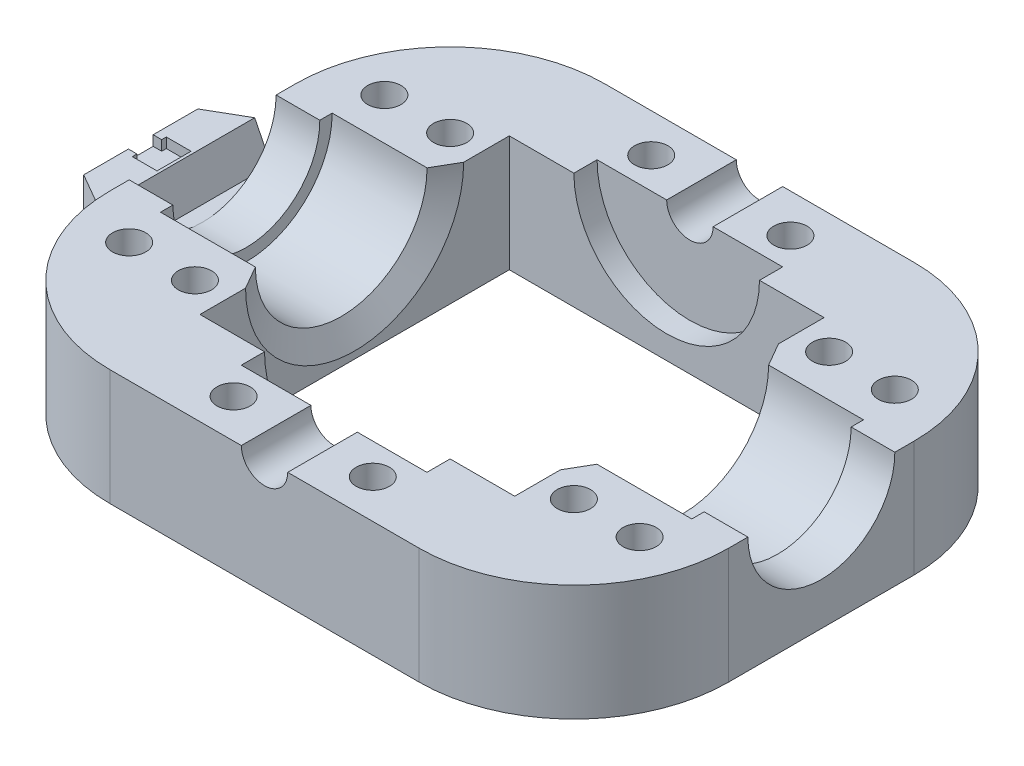
SolidWorks part; units mm, degrees
ref_plane "Спереди" through (0, 0, 0) normal (0, 0, 1) x (1, 0, 0)
ref_plane "Сверху" through (0, 0, 0) normal (0, 1, 0) x (1, 0, 0)
ref_plane "Справа" through (0, 0, 0) normal (1, 0, 0) x (0, 0, -1)
sketch "Sketch1" plane through (0, 0, 0) normal (0, 1, 0) x (1, 0, 0)
  line L1 (40, -32) -> (-40, -32)
  line L2 (40, -32) -> (40, 32)
  line L3 (40, 32) -> (-40, 32)
  line L4 (-40, -32) -> (-40, 32)
  line L5 (40, -32) -> (-40, 32) construction
  line L6 (40, 32) -> (-40, -32) construction
  line L7 (20.35, -20) -> (-20.35, -20)
  line L8 (20.35, -20) -> (20.35, 20)
  line L9 (20.35, 20) -> (-20.35, 20)
  line L10 (-20.35, -20) -> (-20.35, 20)
  line L11 (20.35, -20) -> (-20.35, 20) construction
  line L12 (20.35, 20) -> (-20.35, -20) construction
  point P0 (0, 0)
  point P6 (0, 0)
  dimension "D1" = 80
  dimension "D2" = 64
  dimension "D3" = 40
  dimension "D4" = 40.7
extrude "Boss-Extrude1" add sketch "Sketch1" along normal blind 15
sketch "Sketch3" plane through (0, 15, 0) normal (0, 1, 0) x (1, 0, 0)
  line L0 (-20.35, 0) -> (-40, 0) construction
  line L1 (-20.35, 20) -> (-20.35, -20) construction
  line L2 (-40, 32) -> (-40, -32) construction
  line L3 (20.35, 0) -> (40, 0) construction
  line L4 (20.35, -20) -> (20.35, 20) construction
  line L5 (40, -32) -> (40, 32) construction
  line L10 (20.35, -11.1) -> (34.35, -11.1)
  line L11 (20.35, -11.1) -> (20.35, 0)
  line L12 (20.35, 0) -> (34.35, 0)
  line L13 (34.35, -11.1) -> (34.35, 0)
  line L14 (20.35, -11.1) -> (34.35, 0) construction
  line L15 (20.35, 0) -> (34.35, -11.1) construction
  line L16 (-34.35, -11.1) -> (-20.35, -11.1)
  line L17 (-34.35, -11.1) -> (-34.35, 0)
  line L18 (-34.35, 0) -> (-20.35, 0)
  line L19 (-20.35, -11.1) -> (-20.35, 0)
  line L20 (-34.35, -11.1) -> (-20.35, 0) construction
  line L21 (-34.35, 0) -> (-20.35, -11.1) construction
  point P18 (27.35, -5.55)
  point P23 (-27.35, -5.55)
  dimension "D1" = 14
  dimension "D2" = 11.1
revolve "Cut-Revolve1" cut sketch "Sketch3" angle 360 about L12
sketch "Sketch4" plane through (40, 0, 0) normal (1, 0, 0) x (0, 0, -1)
  line L0 (-32, 15) -> (32, 15) construction
  circle A0 centre (0, 15) radius 9.5
  dimension "D1" = 19
extrude "Cut-Extrude2" cut sketch "Sketch4" against normal through all
sketch "Sketch5" plane through (0, 0, 32) normal (0, 0, 1) x (1, 0, 0)
  line L0 (-40, 15) -> (40, 15) construction
  circle A0 centre (0, 15) radius 3
  dimension "D1" = 6
extrude "Cut-Extrude3" cut sketch "Sketch5" against normal through all
sketch "Sketch8" plane through (0, 15, 0) normal (0, 1, 0) x (1, 0, 0)
  line L1 (-24.5, -16.5) -> (24.5, -16.5) construction
  line L2 (-24.5, -16.5) -> (-24.5, 16.5) construction
  line L3 (-24.5, 16.5) -> (24.5, 16.5) construction
  line L4 (24.5, -16.5) -> (24.5, 16.5) construction
  line L5 (-24.5, -16.5) -> (24.5, 16.5) construction
  line L6 (-24.5, 16.5) -> (24.5, -16.5) construction
  line L7 (-9, 27) -> (9, 27) construction
  line L8 (-9, 27) -> (-9, -27) construction
  line L9 (-9, -27) -> (9, -27) construction
  line L10 (9, 27) -> (9, -27) construction
  line L11 (-9, 27) -> (9, -27) construction
  line L12 (-9, -27) -> (9, 27) construction
  line L13 (33, -16.5) -> (-33, -16.5) construction
  line L14 (33, -16.5) -> (33, 16.5) construction
  line L15 (33, 16.5) -> (-33, 16.5) construction
  line L16 (-33, -16.5) -> (-33, 16.5) construction
  line L17 (33, -16.5) -> (-33, 16.5) construction
  line L18 (33, 16.5) -> (-33, -16.5) construction
  circle A0 centre (24.5, 16.5) radius 2.15
  circle A1 centre (24.5, -16.5) radius 2.15
  circle A2 centre (-24.5, -16.5) radius 2.15
  circle A3 centre (-24.5, 16.5) radius 2.15
  circle A4 centre (9, -27) radius 2.15
  circle A5 centre (-9, -27) radius 2.15
  circle A6 centre (-9, 27) radius 2.15
  circle A7 centre (9, 27) radius 2.15
  circle A8 centre (-33, 16.5) radius 2.15
  circle A9 centre (-33, -16.5) radius 2.15
  circle A10 centre (33, -16.5) radius 2.15
  circle A11 centre (33, 16.5) radius 2.15
  point P0 (0, 0)
  point P10 (0, 0)
  point P16 (0, 0)
  dimension "D3" = 4.3
  dimension "D1" = 33
  dimension "D2" = 49
  dimension "D4" = 18
  dimension "D5" = 54
  dimension "D6" = 66
extrude "Cut-Extrude6" cut sketch "Sketch8" against normal through all
fillet "Fillet1" radius 20 4 edges at (-40, 7.5, 32) (-40, 7.5, -32) (40, 7.5, -32) (40, 7.5, 32)
chamfer "Chamfer1" distance 3 angle 30 2 edges at (-20.35, 3.9, 0) (20.35, 3.9, 0) first distance on face at (-20.35, 8.15, 0) first distance on face at (20.35, 8.15, 0)
sketch "Sketch9" plane through (0, 15, 0) normal (0, 1, 0) x (1, 0, 0)
  line L0 (0, 29.8714) -> (0, -31.0419) construction
  line L1 (-3, 20) -> (-20.35, 20) construction
  line L2 (-12, -23) -> (0, -23)
  line L3 (-12, -23) -> (-12, -20)
  line L4 (-12, -20) -> (0, -20)
  line L5 (0, -23) -> (0, -20)
  line L6 (-12, -23) -> (0, -20) construction
  line L7 (-12, -20) -> (0, -23) construction
  line L8 (-12, 20) -> (0, 20)
  line L9 (-12, 20) -> (-12, 23)
  line L10 (-12, 23) -> (0, 23)
  line L11 (0, 20) -> (0, 23)
  line L12 (-12, 20) -> (0, 23) construction
  line L13 (-12, 23) -> (0, 20) construction
  line L14 (-20.35, -20) -> (-3, -20) construction
  point P3 (-6, -21.5)
  point P8 (-6, 21.5)
  dimension "D1" = 3
  dimension "D2" = 12
revolve "Cut-Revolve2" cut sketch "Sketch9" angle 360 about L0 other way angle 360
sketch "Sketch10" plane through (-40, 0, 0) normal (-1, 0, 0) x (0, 0, 1)
  line L0 (-9.5, 15) -> (9.5, 15) construction
  line L1 (0, 15) -> (0, 0) construction
  line L2 (-12, 0) -> (12, 0) construction
  line L4 (12, 5.5) -> (-12, 5.5)
  line L5 (12, 5.5) -> (12, 0)
  line L6 (12, 0) -> (-12, 0)
  line L7 (-12, 5.5) -> (-12, 0)
  line L8 (12, 5.5) -> (-12, 0) construction
  line L9 (12, 0) -> (-12, 5.5) construction
  arc A0 (-9.5, 15) -> (9.5, 15) centre (0, 15) ccw construction
  point P8 (0, 2.75)
extrude "Boss-Extrude2" add sketch "Sketch10" along normal blind 8
sketch "Sketch12" plane through (-40, 0, 0) normal (-1, 0, 0) x (0, 0, 1)
  line L0 (-9.5, 15) -> (9.5, 15) construction
  line L1 (0, 15) -> (0, 0) construction
  line L3 (12, 9.2) -> (-12, 9.2)
  line L4 (12, 9.2) -> (12, 5.5)
  line L5 (12, 5.5) -> (-12, 5.5)
  line L6 (-12, 9.2) -> (-12, 5.5)
  line L7 (12, 9.2) -> (-12, 5.5) construction
  line L8 (12, 5.5) -> (-12, 9.2) construction
  point P7 (0, 7.35)
  dimension "D1" = 5.8
extrude "Boss-Extrude3" add sketch "Sketch12" along normal up to surface (8 mm away) from offset 2 up to face at (-48, 2.75, 0)
sketch "Sketch13" plane through (0, 9.2, 0) normal (0, 1, 0) x (1, 0, 0)
  line L0 (-42, 0) -> (-48, 0) construction
  line L1 (-42, -12) -> (-42, 12) construction
  line L2 (-48, 12) -> (-48, -12) construction
  line L3 (-46.9, 2.2) -> (-46.9, 1.6)
  line L4 (-46.9, -2.2) -> (-43.7, -2.2)
  line L5 (-46.9, 1.6) -> (-48, 1.6)
  line L6 (-46.9, 2.2) -> (-43.7, 2.2)
  line L7 (-43.7, -2.2) -> (-43.7, 2.2)
  line L8 (-46.9, -2.2) -> (-43.7, 2.2) construction
  line L9 (-46.9, 2.2) -> (-43.7, -2.2) construction
  line L10 (-46.9, -2.2) -> (-46.9, -1.6)
  line L11 (-46.9, -1.6) -> (-48, -1.6)
  line L12 (-48, -1.6) -> (-48, -12)
  line L13 (-48, -12) -> (-42, -12)
  line L14 (-42, -12) -> (-42, 12)
  line L15 (-42, 12) -> (-48, 12)
  line L16 (-48, 12) -> (-48, 1.6)
  point P6 (-45.3, 0)
  dimension "D1" = 3.2
  dimension "D2" = 4.4
  dimension "D3" = 3.2
  dimension "D4" = 2.7
extrude "Boss-Extrude4" add sketch "Sketch13" along normal blind 1.3
chamfer "Chamfer2" distance 5 angle 15 1 edges at (-42, 10.5, 0) first distance on face at (-42, 8, 0)
chamfer "Chamfer3" distance 8 angle 30 2 edges at (-48, 5.25, 12) (-48, 5.25, -12) first distance on face at (-43.5566, 5.3333, 12) first distance on face at (-43.5566, 5.3333, -12)
